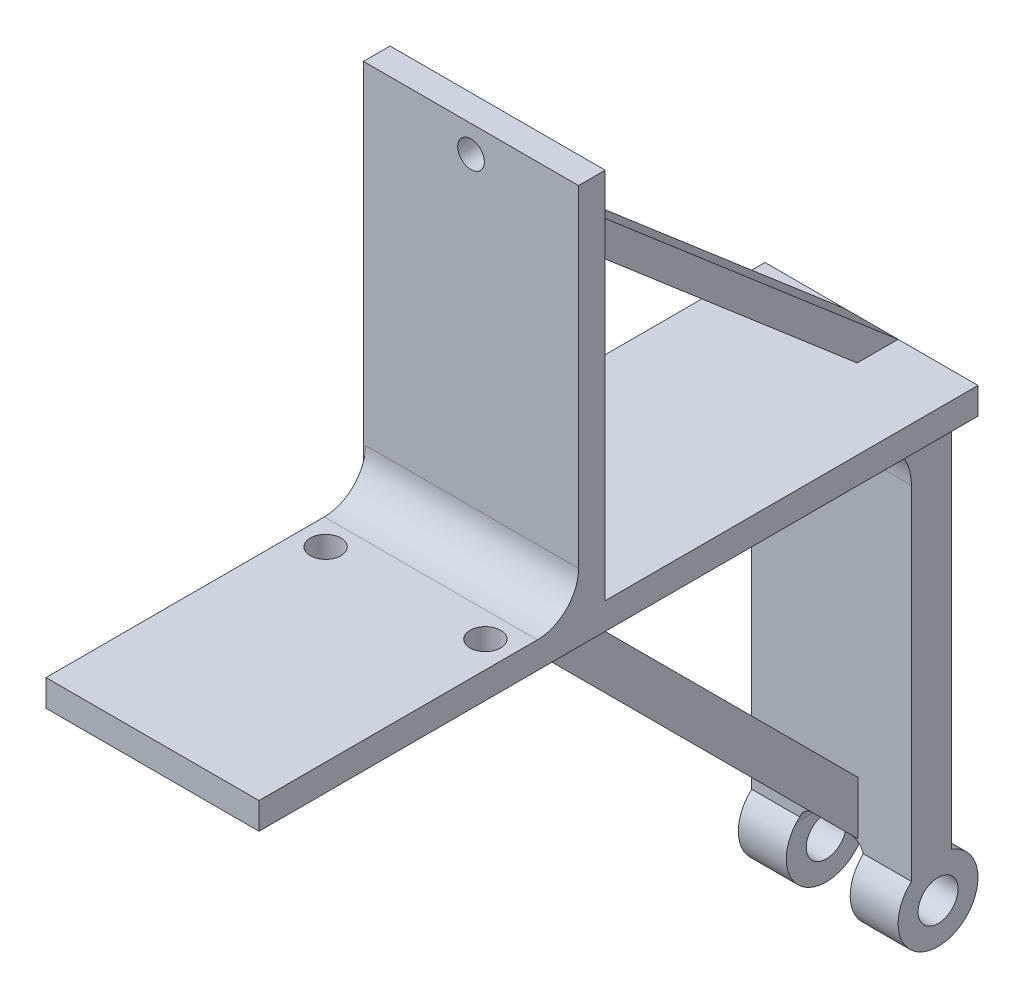
SolidWorks part; units mm, degrees
material "Plain Carbon Steel"
ref_plane "Front" through (0, 0, 0) normal (0, 0, 1) x (1, 0, 0)
ref_plane "Top" through (0, 0, 0) normal (0, 1, 0) x (1, 0, 0)
ref_plane "Right" through (0, 0, 0) normal (1, 0, 0) x (0, 0, -1)
sketch "Sketch2" plane through (0, 0, 0) normal (0, 1, 0) x (1, 0, 0)
  line L1 (0, 0) -> (50.8, 0)
  line L2 (0, 0) -> (0, 92.075)
  line L3 (0, 92.075) -> (50.8, 92.075)
  line L4 (50.8, 0) -> (50.8, 92.075)
  dimension "D1" = 92.075
  dimension "D2" = 50.8
extrude "Boss-Extrude1" add sketch "Sketch2" along normal blind 6.35
sketch "Sketch3" plane through (0, 6.35, 0) normal (0, 1, 0) x (1, 0, 0)
  line L0 (50.8, 0) -> (50.8, 92.075) construction
  line L1 (-0.5006, 41.275) -> (50.8, 41.275)
  line L2 (-0.5006, 41.275) -> (-0.5006, 34.925)
  line L3 (-0.5006, 34.925) -> (50.8, 34.925)
  line L4 (50.8, 41.275) -> (50.8, 34.925)
  line L5 (50.8, 92.075) -> (0, 92.075) construction
  point P7 (0, 0)
  point P8 (0, 0)
  dimension "D1" = 6.35
  dimension "D2" = 50.8
extrude "Boss-Extrude2" add sketch "Sketch3" along normal blind 88.9
fillet "Fillet1" radius 9.8425 1 edges at (25.4, 6.35, -34.925)
sketch "Sketch4" plane through (0, 0, -92.075) normal (0, 0, -1) x (-1, 0, 0)
  line L0 (-50.8, 6.35) -> (-50.8, 0) construction
  line L1 (0, 0) -> (-50.8, 0)
  line L2 (0, 0) -> (0, 6.35)
  line L3 (0, 6.35) -> (-50.8, 6.35)
  line L4 (-50.8, 0) -> (-50.8, 6.35)
  dimension "D1" = 6.35
extrude "Boss-Extrude3" add sketch "Sketch4" along normal blind 38.1
ref_plane "Plane1" through (25.4, 0, 0) normal (1, 0, 0) x (0, 0, -1)
sketch "Sketch5" plane through (25.4, 0, 0) normal (1, 0, 0) x (0, 0, -1)
  line L0 (0, 0) -> (130.175, 0)
  line L3 (130.175, 0) -> (123.825, 0)
  line L4 (127, 0) -> (127, -101.6)
  line L5 (127, -101.6) -> (-38.1, -101.6)
  line L6 (-38.1, -101.6) -> (3.175, 0)
  line L7 (0, 0) -> (130.175, 0) construction
  circle A0 centre (127, -101.6) radius 4.7625
  circle A1 centre (127, -101.6) radius 9.525
  point P6 (123.825, 0)
  point P7 (6.35, 0)
  point P8 (127, 0)
  point P19 (127, -92.075)
  dimension "D7" = 9.525
  dimension "D8" = 19.05
  dimension "D1" = 6.35
  dimension "D2" = 6.35
  dimension "D3" = 3.175
  dimension "D4" = 3.175
  dimension "D5" = 101.6
  dimension "D6" = 165.1
sketch "Sketch7" plane through (0, 0, 0) normal (0, -1, 0) x (-1, 0, 0)
  line L0 (-50.8, 130.175) -> (0, 130.175) construction
  line L1 (-25.4, 130.175) -> (-44.45, 130.175)
  line L2 (-25.4, 130.175) -> (-25.4, 120.65)
  line L3 (-25.4, 120.65) -> (-44.45, 120.65)
  line L4 (-44.45, 130.175) -> (-44.45, 120.65)
  line L6 (-25.4, 120.65) -> (-6.35, 120.65)
  line L7 (-25.4, 120.65) -> (-25.4, 130.175)
  line L8 (-25.4, 130.175) -> (-6.35, 130.175)
  line L9 (-6.35, 120.65) -> (-6.35, 130.175)
  line M10 (0, 130.175) -> (-50.8, 130.175)
  dimension "D1" = 19.05
  dimension "D2" = 9.525
extrude "Boss-Extrude4" add sketch "Sketch7" along normal up to vertex (92.075 mm away) contours L6 L9 L2 M10 | L4 L3 L2 M10 region at (34.925, 0, -125.4125) region at (15.875, 0, -125.4125) up to point (25.4, -92.075, -127)
extrude "Boss-Extrude7" add sketch "Sketch5" against normal up to surface (19.05 mm away) from offset 7.62 separate body contours L4 A0 L5 | L5 A0 L4 | A1 region at (25.4, -99.5787, -124.9787) region at (25.4, -102.2738, -127.6738) up to face at (6.35, -46.0375, -125.4125) offset against normal yes
extrude "Boss-Extrude8" add sketch "Sketch5<6>" along normal up to surface (19.05 mm away) from offset 7.62 separate body contours L5 A1 L4 A0 | L4 A1 L5 A0 region at (25.4, -96.8837, -122.2837) region at (25.4, -101.8694, -119.8563) up to face at (44.45, -46.0375, -125.4125)
sketch "Sketch5<6>" plane through (25.4, 0, 0) normal (1, 0, 0) x (0, 0, -1) same geometry as "Sketch5"
sketch "Sketch11" plane through (0, -92.075, 0) normal (0, -1, 0) x (1, 0, 0)
  line L0 (33.02, -117.475) -> (33.02, -136.525) construction
  line L1 (44.45, -130.175) -> (6.35, -130.175)
  line L2 (44.45, -130.175) -> (44.45, -120.65)
  line L3 (44.45, -120.65) -> (6.35, -120.65)
  line L4 (6.35, -130.175) -> (6.35, -120.65)
  line L5 (33.02, -130.175) -> (44.45, -130.175)
  line L6 (33.02, -130.175) -> (33.02, -120.65)
  line L7 (33.02, -120.65) -> (44.45, -120.65)
  line L8 (44.45, -130.175) -> (44.45, -120.65)
  line L9 (6.35, -130.175) -> (17.78, -130.175)
  line L10 (6.35, -130.175) -> (6.35, -120.65)
  line L11 (6.35, -120.65) -> (17.78, -120.65)
  line L12 (17.78, -130.175) -> (17.78, -120.65)
  line L13 (17.78, -136.525) -> (17.78, -117.475) construction
  line M10 (44.45, -130.175) -> (44.45, -120.65)
  line M11 (44.45, -120.65) -> (6.35, -120.65)
  line M12 (6.35, -120.65) -> (6.35, -130.175)
  line M13 (6.35, -130.175) -> (44.45, -130.175)
extrude "Boss-Extrude9" add sketch "Sketch11" along normal up to surface (2.4255 mm away) contours L12 M13 M11 M12 | L6 L1 M10 M11 region at (38.735, -92.075, -125.4125) region at (12.065, -92.075, -125.4125) up to face at (6.35, -101.6, -136.525)
sketch "Sketch13" plane through (25.4, 0, 0) normal (1, 0, 0) x (0, 0, -1)
  line L0 (123.825, 0) -> (28.575, 0)
  line L1 (120.65, -92.075) -> (28.575, 0)
  line L2 (41.275, 0) -> (120.65, -79.375)
  line L3 (120.65, -92.075) -> (120.65, -79.375)
  line L4 (41.275, 0) -> (28.575, 0)
  dimension "D1" = 95.25
  dimension "D2" = 12.7
  dimension "D3" = 12.7
extrude "Boss-Extrude10" add sketch "Sketch13" along normal blind 6.35 and the other way blind 6.35 contours L1 L3 L2 L0 region at (25.4, -42.9409, -77.7091)
sketch "Sketch15" plane through (25.4, 0, 0) normal (1, 0, 0) x (0, 0, -1)
  line L1 (0, 0) -> (12.7, 0)
  line L2 (0, 0) -> (0, -6.35)
  line L3 (0, -6.35) -> (12.7, -6.35)
  line L4 (12.7, 0) -> (12.7, -6.35)
  circle A0 centre (6.35, -6.35) radius 6.35
  circle A1 centre (6.35, -6.35) radius 3.175
  dimension "D2" = 6.35
  dimension "D1" = 6.35
  dimension "D3" = 12.7
extrude "Boss-Extrude11" add sketch "Sketch15" along normal blind 6.35 from offset 6.35 contours A1 L3 A0 | A1 L3 A0 | A0 L1 L2 | A0 L4 L1 region at (25.4, -1.4184, -1.4184) region at (25.4, -1.4184, -11.2816) region at (25.4, -1.9603, -10.7397) region at (25.4, -6.492, -1.5875)
extrude "Boss-Extrude12" add sketch "Sketch15<3>" against normal blind 6.35 from offset 6.35 contours A1 L3 A0 | A1 L3 A0 | A0 L1 L2 | A0 L4 L1 region at (25.4, -1.4184, -1.4184) region at (25.4, -1.4184, -11.2816) region at (25.4, -1.9603, -10.7397) region at (25.4, -6.492, -1.5875) offset against normal yes
sketch "Sketch15<3>" plane through (25.4, 0, 0) normal (1, 0, 0) x (0, 0, -1) same geometry as "Sketch15"
sketch "Sketch17" plane through (0, 0, 0) normal (0, -1, 0) x (-1, 0, 0)
  line L2 (-50.8, 19.05) -> (0, 19.05)
  line L3 (-50.8, 0) -> (-50.8, 130.175) construction
  line L4 (0, 130.175) -> (0, 0) construction
  line L5 (-38.1, 0) -> (-50.8, 0) construction
  circle A1 centre (-44.45, 19.05) radius 3.6573
  circle A2 centre (-6.35, 19.05) radius 3.6573
  dimension "D3" = 19.05
  dimension "D4" = 6.35
  dimension "D5" = 6.35
sketch "Sketch18" plane through (0, 0, 0) normal (0, 0, 1) x (1, 0, 0)
  line L1 (50.8, 0) -> (0, 0)
  line L2 (50.8, 0) -> (50.8, 6.35)
  line L3 (50.8, 6.35) -> (0, 6.35)
  line L4 (0, 0) -> (0, 6.35)
extrude "Boss-Extrude13" add sketch "Sketch18" along normal blind 76.2 from surface starting at face at (16.7665, 39.2642, -34.925)
extrude "Cut-Extrude4" cut sketch "Sketch17" against normal up to surface (6.35 mm away) contours L2 A1 | L2 A1 | A2 region at (44.45, 0, -20.6022) region at (44.45, 0, -17.4978) up to face at (25.4, 6.35, 8.0963)
sketch "Sketch19" plane through (0, 0, -41.275) normal (0, 0, -1) x (-1, 0, 0)
  line L0 (-50.8, 95.25) -> (-50.8, 6.35) construction
  line L1 (0.5006, 95.25) -> (-50.8, 95.25)
  line L2 (0.5006, 95.25) -> (0.5006, 88.9)
  line L3 (0.5006, 88.9) -> (-50.8, 88.9)
  line L4 (-50.8, 95.25) -> (-50.8, 88.9)
  circle A0 centre (-25.1497, 88.9) radius 6.35
  circle A1 centre (-25.1497, 88.9) radius 3.175
  dimension "D2" = 6.35
  dimension "D1" = 6.35
extrude "Cut-Extrude5" cut sketch "Sketch19" against normal up to surface (6.35 mm away) contours L3 A1 | L3 A1 region at (25.1497, 87.5525, -41.275) region at (25.1497, 90.2475, -41.275) up to face at (16.7665, 39.2642, -34.925)
sketch "Sketch20" plane through (25.4, 0, 0) normal (1, 0, 0) x (0, 0, -1)
  line L0 (41.275, 82.55) -> (130.175, 6.35)
  line L1 (41.275, 95.25) -> (41.275, 6.35) construction
  line L2 (130.175, 6.35) -> (120.4176, 6.35)
  line L3 (41.275, 6.35) -> (130.175, 6.35) construction
  line L4 (120.4176, 6.35) -> (41.275, 74.1866)
  line L5 (41.275, 74.1866) -> (41.275, 82.55)
  dimension "D1" = 76.2
  dimension "D2" = 6.35
extrude "Boss-Extrude14" add sketch "Sketch20" along normal blind 6.35 and the other way blind 6.35
fillet "Fillet2" radius 12.7 1 edges at (25.4, 0, -120.65)
fillet "Fillet3" radius 3.175 2 edges at (33.02, -92.075, -125.4125) (17.78, -92.075, -125.4125)
